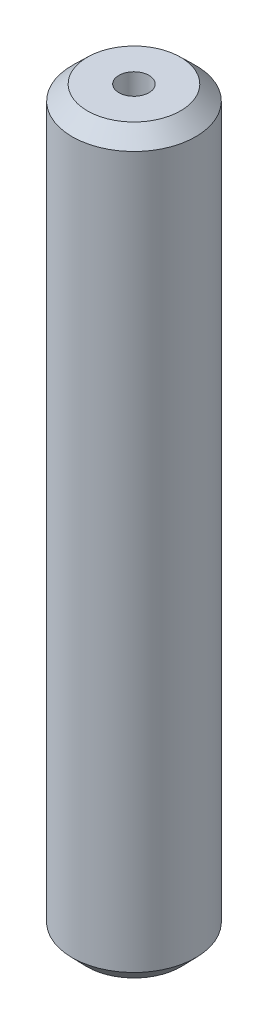
SolidWorks part; units mm, degrees
ref_plane "Front Plane" through (0, 0, 0) normal (0, 0, 1) x (1, 0, 0)
ref_plane "Top Plane" through (0, 0, 0) normal (0, 1, 0) x (1, 0, 0)
ref_plane "Right Plane" through (0, 0, 0) normal (1, 0, 0) x (0, 0, -1)
sketch "Sketch1" plane through (0, 0, 0) normal (0, 1, 0) x (1, 0, 0)
  circle A0 centre (0, 0) radius 5
  dimension "SHAFT_OD" = 10
extrude "Boss-Extrude1" add sketch "Sketch1" along normal blind 59.9678
sketch "Sketch2" plane through (0, 0, 0) normal (0, 1, 0) x (1, 0, 0)
  circle A0 centre (0, 0) radius 1.2179
  dimension "BORE_D" = 2.4358
extrude "Cut-Extrude1" cut sketch "Sketch2" along normal through all
chamfer "Chamfer1" distance 1.1956 angle 45.85 2 edges at (0, 59.9678, 5) (0, 0, 5) first distance on face at (0, 59.9678, 5) first distance on face at (0, 0, 1.2179)
